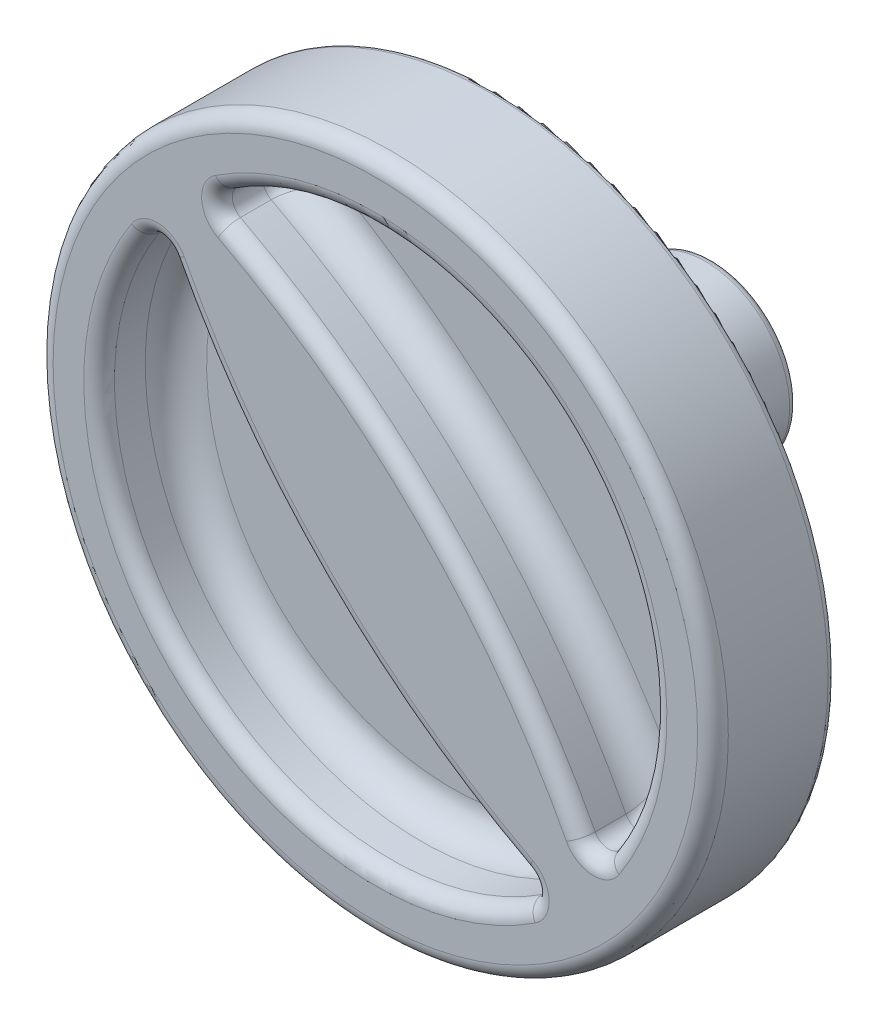
SolidWorks part; units mm, degrees
ref_plane "Front Plane" through (0, 0, 0) normal (0, 0, 1) x (1, 0, 0)
ref_plane "Top Plane" through (0, 0, 0) normal (0, 1, 0) x (1, 0, 0)
ref_plane "Right Plane" through (0, 0, 0) normal (1, 0, 0) x (0, 0, -1)
sketch "Sketch2" plane through (0, 0, 0) normal (0, 0, 1) x (1, 0, 0)
  line L0 (2, 1.5) -> (-2, 1.5)
  line L1 (-2, -1.5) -> (2, -1.5)
  circle A0 centre (0, 0) radius 2.5
  circle A1 centre (0, 0) radius 5
  dimension "D1" = 5
  dimension "D4" = 10
  dimension "D2" = 3
  dimension "D3" = 1.5
extrude "Boss-Extrude1" add sketch "Sketch2" along normal blind 5 contours A1 A0 | L0 A0 | L1 A0 region at (0, 1.9078, 0) region at (0, -1.9078, 0) region at (-4.8586, 0, 0)
sketch "Sketch4" plane through (0, 0, 5) normal (0, 0, 1) x (1, 0, 0)
  circle A0 centre (0, 0) radius 5
extrude "Boss-Extrude2" add sketch "Sketch4" along normal blind 3
sketch "Sketch5" plane through (0, 0, 8) normal (0, 0, 1) x (1, 0, 0)
  circle A0 centre (0, 0) radius 5
  circle A1 centre (0, 0) radius 22
  dimension "D1" = 44
extrude "Boss-Extrude3" add sketch "Sketch5" against normal blind 8
fillet "Fillet1" radius 1 1 edges at (22, 0, 8)
sketch "Sketch6" plane through (0, 0, 8) normal (0, 0, 1) x (1, 0, 0)
  line L0 (-14.8492, 14.8492) -> (14.8492, -14.8492) construction
  arc A1 (-11.2349, 14.0633) -> (14.0633, -11.2349) centre (-35.3553, -35.3553) cw
  arc A2 (-11.2349, 14.0633) -> (14.0633, -11.2349) centre (0, 0) cw
  arc A3 (-14.0633, 11.2349) -> (11.2349, -14.0633) centre (0, 0) ccw
  arc A4 (-14.0633, 11.2349) -> (11.2349, -14.0633) centre (35.3553, 35.3553) ccw
  dimension "D2" = 18
  dimension "D3" = 50
  dimension "D1" = 0
  dimension "D4" = 2
extrude "Cut-Extrude1" cut sketch "Sketch6" against normal blind 5
fillet "Fillet6" radius 1 4 edges at (-14.0633, 11.2349, 5.5) (11.2349, -14.0633, 5.5) (14.0633, -11.2349, 5.5) (-11.2349, 14.0633, 5.5)
fillet "Fillet7" radius 1 8 edges at (14.1673, -10.3216, 8) (3.5291, 3.5291, 8) (-10.3216, 14.1673, 8) (-14.1673, 10.3216, 8) (-3.5291, -3.5291, 8) (10.3216, -14.1673, 8) (12.7279, 12.7279, 8) (-12.7279, -12.7279, 8)
fillet "Fillet8" radius 2 8 edges at (10.3216, -14.1673, 3) (-12.7279, -12.7279, 3) (-14.1673, 10.3216, 3) (-3.5291, -3.5291, 3) (-10.3216, 14.1673, 3) (12.7279, 12.7279, 3) (14.1673, -10.3216, 3) (3.5291, 3.5291, 3)
sketch "Sketch7" plane through (0, 0, 0) normal (0, 0, -1) x (-1, 0, 0)
  line L0 (-2, 1.5) -> (2, 1.5)
  line L1 (-2, -1.5) -> (1.5, -1.5)
  line L2 (2, -1.5) -> (-2, -1.5) construction
  circle A0 centre (0, 0) radius 5.5
  circle A1 centre (0, 0) radius 2.1213
  arc M3 (-2, -1.5) -> (-2, 1.5) centre (0, 0) cw
  line M4 (-2, 1.5) -> (2, 1.5)
  arc M5 (2, 1.5) -> (2, -1.5) centre (0, 0) cw
  line M6 (2, -1.5) -> (-2, -1.5)
  dimension "D1" = 11
extrude "Boss-Extrude4" add sketch "Sketch7" along normal blind 14 contours A0 A1 M5 M3 | A1 M4 | A1 M6 region at (0, 1.7519, 0) region at (0, -1.7519, 0) region at (5.3444, 0, 0)
fillet "Fillet9" radius 0.5 3 edges at (22, 0, 0) (5.5, 0, 0) (-5.5, 0, -14)
ref_plane "Plane1" through (0, 0, -7.75) normal (0, 0, -1) x (-1, 0, 0)
sketch "Sketch8" plane through (0, 0, -7.75) normal (0, 0, -1) x (-1, 0, 0)
  circle A0 centre (0, 0) radius 5.5
  circle A1 centre (0, 0) radius 4.8
  dimension "D1" = 9.6
  dimension "D2" = 11
extrude "Cut-Extrude2" cut sketch "Sketch8" along normal blind 1.1
